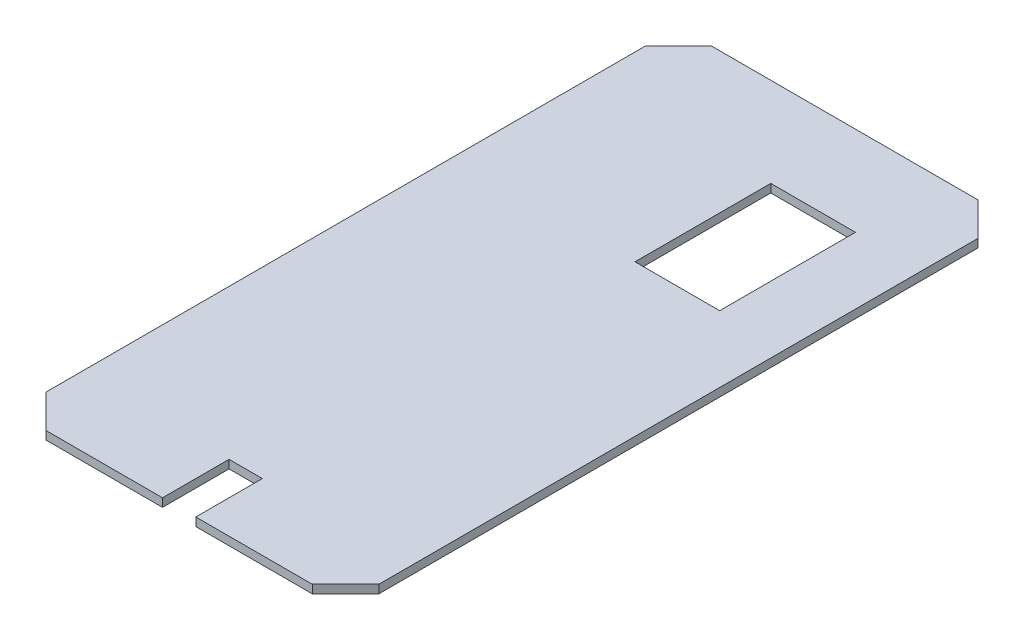
SolidWorks part; units mm, degrees
ref_plane "Front Plane" through (0, 0, 0) normal (0, 0, 1) x (1, 0, 0)
ref_plane "Top Plane" through (0, 0, 0) normal (0, 1, 0) x (1, 0, 0)
ref_plane "Right Plane" through (0, 0, 0) normal (1, 0, 0) x (0, 0, -1)
sketch "Sketch2" plane through (0, 0, 0) normal (0, 1, 0) x (1, 0, 0)
  line L0 (0, 12.7) -> (0, 241.3)
  line L1 (12.7, 254) -> (114.3, 254)
  line L2 (127, 241.3) -> (127, 12.7)
  line L3 (114.3, 0) -> (12.7, 0)
  line L4 (0, 241.3) -> (12.7, 254)
  line L5 (114.3, 254) -> (127, 241.3)
  line L6 (127, 12.7) -> (114.3, 0)
  line L7 (12.7, 0) -> (0, 12.7)
  line L8 (63.5, 254) -> (63.5, -26.6567) construction
  line L10 (0, 127) -> (136.1553, 127) construction
  line L17 (57.15, 25.4) -> (69.85, 25.4)
  line L18 (57.15, 25.4) -> (57.15, 0)
  line L19 (57.15, 0) -> (69.85, 0)
  line L20 (69.85, 25.4) -> (69.85, 0)
  line L21 (57.15, 25.4) -> (69.85, 0) construction
  line L22 (57.15, 0) -> (69.85, 25.4) construction
  line L23 (69.3167, 219.9196) -> (101.627, 219.9196)
  line L24 (69.3167, 219.9196) -> (69.3167, 168.1143)
  line L25 (69.3167, 168.1143) -> (101.627, 168.1143)
  line L26 (101.627, 219.9196) -> (101.627, 168.1143)
  line L27 (69.3167, 219.9196) -> (101.627, 168.1143) construction
  line L28 (69.3167, 168.1143) -> (101.627, 219.9196) construction
  point P0 (63.5, 127)
  point P1 (85.4719, 194.0169)
  point P3 (63.5, 12.7)
  point P37 (127, 127)
  point P42 (63.5, 0)
  dimension "D14" = 101.6
  dimension "D16" = 12.7
  dimension "D17" = 254
  dimension "D22" = 228.6
  dimension "D36" = 101.6
  dimension "D37" = 228.6
  dimension "D7" = 127
  dimension "D15" = 12.7
  dimension "D4" = 25.4
  dimension "D5" = 12.7
extrude "Boss-Extrude1" add sketch "Sketch2" along normal blind 3.175 contours L7 L3 L6 L2 L5 L1 L4 L0 region at (62.2716, 0, -124.4847)
